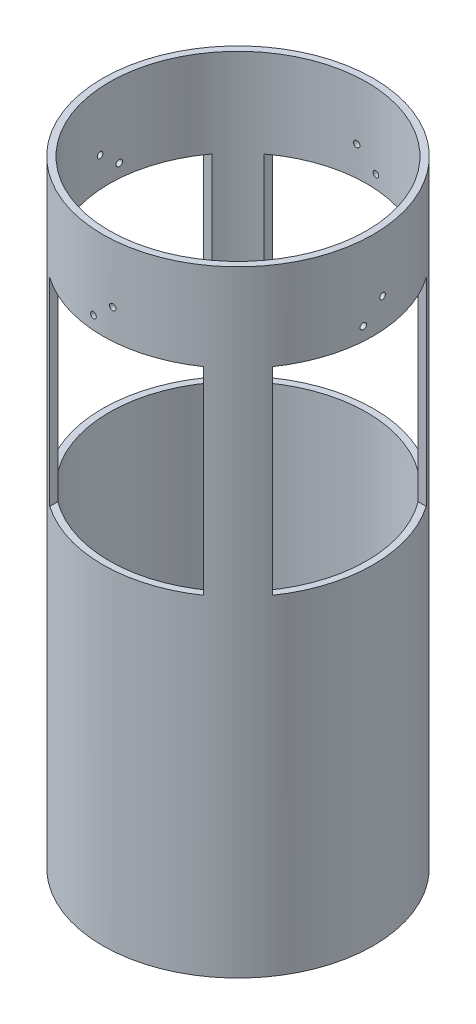
SolidWorks part; units mm, degrees
ref_plane "Front Plane" through (0, 0, 0) normal (0, 0, 1) x (1, 0, 0)
ref_plane "Top Plane" through (0, 0, 0) normal (0, 1, 0) x (1, 0, 0)
ref_plane "Right Plane" through (0, 0, 0) normal (1, 0, 0) x (0, 0, -1)
sketch "Sketch1" plane through (0, 0, 0) normal (0, 1, 0) x (1, 0, 0)
  circle A0 centre (0, 0) radius 78.105
  circle A1 centre (0, 0) radius 74.295
extrude "Boss-Extrude1" add sketch "Sketch1" along normal blind 177.8
sketch "Sketch5" plane through (0, 0, 0) normal (0, -1, 0) x (1, 0, 0)
  line L0 (0, 78.105) -> (0, -78.105) construction
  circle A0 centre (0, 0) radius 78.105 construction
ref_plane "Plane2" through (0, 0, -78.105) normal (0, 0, -1) x (-1, 0, 0)
sketch "Sketch6" plane through (0, 0, -78.105) normal (0, 0, -1) x (-1, 0, 0)
  line L0 (0, 177.8) -> (0, 127) construction
  line L1 (74.295, 177.8) -> (-74.295, 177.8) construction
  line L2 (-44.45, 127) -> (44.45, 127)
  line L13 (44.45, 127) -> (44.45, 12.7)
  line L16 (-44.45, 12.7) -> (44.45, 12.7)
  line L17 (-44.45, 127) -> (-44.45, 12.7)
  point P15 (0, 127)
extrude "Cut-Extrude6" cut sketch "Sketch6" against normal blind 20.574
pattern_circular "CirPattern9" count 4 over 360 about axis through (0, 0, 0) along (0, 1, 0) of "Cut-Extrude6"
sketch "Sketch7" plane through (0, 0, -78.105) normal (0, 0, -1) x (-1, 0, 0)
  line L0 (0, 0) -> (0, 127) construction
  line L1 (0, 127) -> (0, 134.62) construction
  line L2 (0, 127) -> (0, 144.145) construction
  line L3 (0, 127) -> (0, 185.42) construction
  line L4 (0, 134.62) -> (-5.5562, 134.62) construction
  line L5 (0, 144.145) -> (5.5562, 144.145) construction
  circle A2 centre (0, 185.42) radius 1.7526
  circle A3 centre (5.5562, 144.145) radius 1.7526
  circle A4 centre (-5.5562, 134.62) radius 1.7526
  point P6 (0, 134.62)
extrude "Cut-Extrude7" cut sketch "Sketch7" against normal blind 17.78 contours A4 | A3 | A2
pattern_circular "CirPattern10" count 4 over 360 about axis through (0, 177.8, 0) along (0, 1, 0) of "Cut-Extrude7"
sketch "Sketch8" plane through (0, 0, 0) normal (0, -1, 0) x (1, 0, 0)
  circle A0 centre (0, 0) radius 78.105
  circle A1 centre (0, 0) radius 74.295
extrude "Boss-Extrude2" add sketch "Sketch8" along normal blind 25.4
sketch "Sketch9" plane through (0, -25.4, 0) normal (0, -1, 0) x (1, 0, 0)
  circle A0 centre (0, 0) radius 78.105
  circle A1 centre (0, 0) radius 74.295
extrude "Boss-Extrude3" add sketch "Sketch9" along normal blind 152.4
